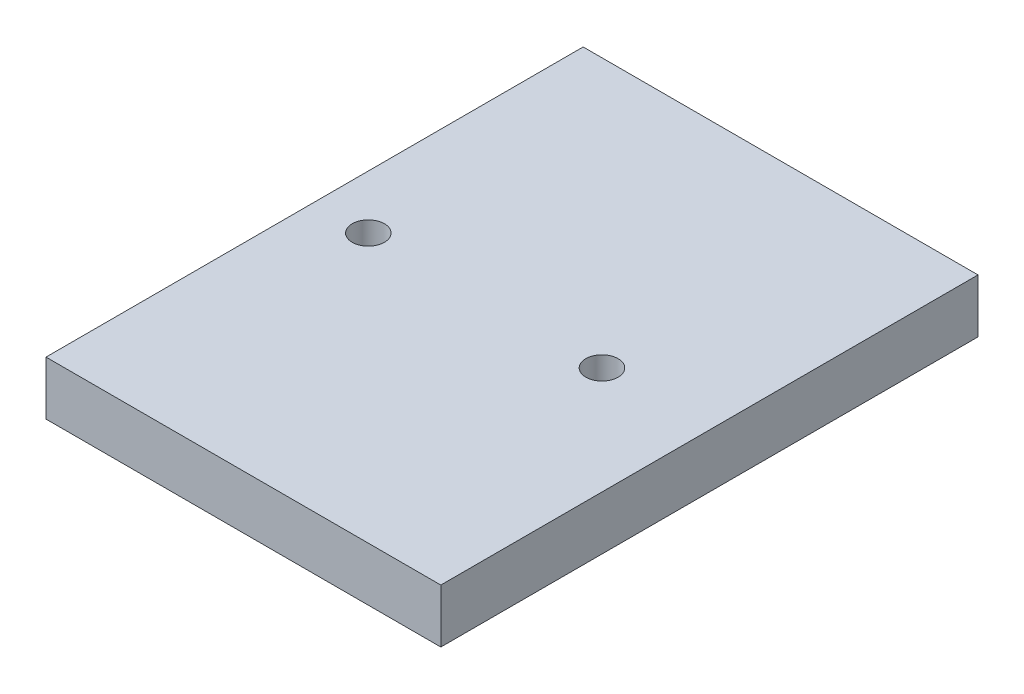
SolidWorks part; units mm, degrees
other "标注1"
sketch "草图3" plane through (0, 5, 29.5) normal (-0.6417, 0.7662, 0.0339) x (0.7661, 0.6384, 0.0747)
ref_plane "前视基准面" through (0, 0, 0) normal (0, 0, 1) x (1, 0, 0)
ref_plane "上视基准面" through (0, 0, 0) normal (0, 1, 0) x (1, 0, 0)
ref_plane "右视基准面" through (0, 0, 0) normal (1, 0, 0) x (0, 0, -1)
other "Configuration Table"
sketch "草图4" plane through (0, 0, 0) normal (0, 1, 0) x (1, 0, 0)
  line L1 (0, 0) -> (-36.75, 0)
  line L2 (0, 0) -> (0, -10)
  line L3 (0, -10) -> (-36.75, -10)
  line L4 (-36.75, 0) -> (-36.75, -10)
  circle A0 centre (-31.75, -5) radius 1.5
  circle A1 centre (-10, -5) radius 1.5
  circle A8 centre (-31.75, -5) radius 2.25
  circle A9 centre (-10, -5) radius 2.25
  dimension "D3" = 3
  dimension "D4" = 4.5
  dimension "D1" = 10
  dimension "D2" = 36.75
extrude "凸台-拉伸1" add sketch "草图4" along normal blind 5 contours L4 L3 L2 L1 | A0 | A1
sketch "草图5" plane through (0, 0, 10) normal (0, 0, 1) x (1, 0, 0)
  line L1 (-36.75, 5) -> (0, 5)
  line L2 (-36.75, 5) -> (-36.75, 0)
  line L3 (-36.75, 0) -> (0, 0)
  line L4 (0, 5) -> (0, 0)
extrude "凸台-拉伸2" add sketch "草图5" along normal blind 20
extrude "凸台-拉伸3" add sketch "草图5<2>" against normal blind 20 from surface starting at face at (-18.375, 2.5, 0)
sketch "草图5<2>" plane through (0, 0, 10) normal (0, 0, 1) x (1, 0, 0) same geometry as "草图5"
sketch "草图6" plane through (-36.75, 0, 0) normal (-1, 0, 0) x (0, 0, 1)
  line L0 (-20, 5) -> (-20, 0) construction
  line L1 (30, 5) -> (30, 0) construction
  circle A0 centre (-10, 2.5) radius 1
  circle A1 centre (20, 2.5) radius 1
  point P6 (-20, 2.5)
  dimension "D1" = 2
  dimension "D2" = 10
  dimension "D3" = 10
extrude "切除-拉伸1" cut sketch "草图6" against normal blind 4
extrude "切除-拉伸2" cut sketch "草图4<5>" along normal blind 2 contours A8 | A9
sketch "草图4<5>" plane through (0, 0, 0) normal (0, 1, 0) x (1, 0, 0) same geometry as "草图4"
